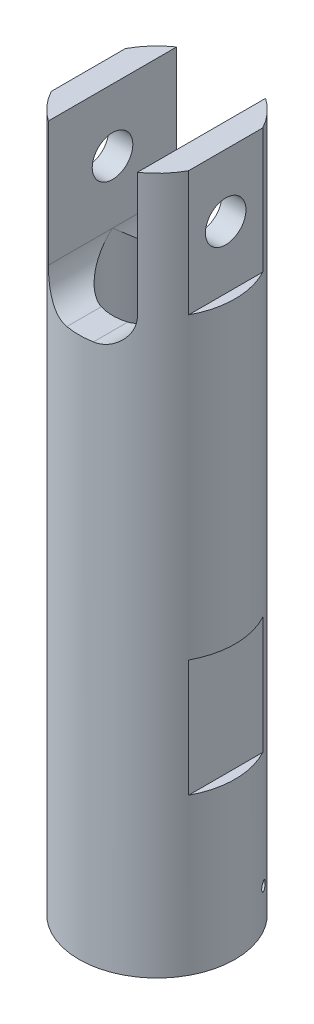
SolidWorks part; units mm, degrees
material "6061-T6 (SS)"
ref_plane "Front Plane" through (0, 0, 0) normal (0, 0, 1) x (1, 0, 0)
ref_plane "Top Plane" through (0, 0, 0) normal (0, 1, 0) x (1, 0, 0)
ref_plane "Right Plane" through (0, 0, 0) normal (1, 0, 0) x (0, 0, -1)
sketch "Sketch1" plane through (0, 0, 0) normal (0, 1, 0) x (1, 0, 0)
  circle A0 centre (0, 0) radius 4.826
  circle A1 centre (0, 0) radius 12.7
  dimension "D1" = 9.652
  dimension "D2" = 25.4
extrude "Socket Head Stop" add sketch "Sketch1" along normal blind 5.08
sketch "Sketch2" plane through (0, 0, 0) normal (0, 1, 0) x (1, 0, 0)
  circle A0 centre (0, 0) radius 12.7 construction
  circle A1 centre (0, 0) radius 12.7
  circle A2 centre (0, 0) radius 7.239
  dimension "D1" = 14.478
extrude "Main Body" add sketch "Sketch2" along normal blind 100.7072
sketch "Sketch6" plane through (0, 0, 0) normal (1, 0, 0) x (0, 0, -1)
  line L0 (-12.7, 0) -> (12.7, 0) construction
  circle A0 centre (0, 90.5472) radius 3.302
  dimension "D2" = 6.604
  dimension "D1" = 90.5472
extrude "Rod End Mounting Holes" cut sketch "Sketch6" against normal through all both and the other way through all
sketch "Sketch3" plane through (0, 0, 0) normal (0, 0, 1) x (1, 0, 0)
  line L0 (-7.239, 100.7072) -> (-7.239, 80.3872)
  line L1 (7.239, 100.7072) -> (-7.239, 100.7072) construction
  line L2 (-2.159, 75.3072) -> (2.159, 75.3072)
  line L3 (7.239, 100.7072) -> (7.239, 80.3872)
  line L4 (12.7, 100.7072) -> (-12.7, 100.7072) construction
  line L5 (12.7, 100.7072) -> (-12.7, 100.7072)
  line L6 (-12.7, 0) -> (12.7, 0) construction
  line L7 (7.239, 100.7072) -> (-7.239, 100.7072)
  line L8 (-12.7, 100.7072) -> (-12.7, 93.8492) construction
  line L9 (-12.7, 100.7072) -> (-11.176, 100.7072)
  line L10 (-12.7, 100.7072) -> (-12.7, 80.3872)
  line L11 (-12.7, 80.3872) -> (-11.176, 80.3872)
  line L12 (-11.176, 100.7072) -> (-11.176, 80.3872)
  line L13 (12.7, 93.8492) -> (12.7, 100.7072) construction
  line L14 (12.7, 100.7072) -> (11.176, 100.7072)
  line L15 (12.7, 100.7072) -> (12.7, 80.3872)
  line L16 (12.7, 80.3872) -> (11.176, 80.3872)
  line L17 (11.176, 100.7072) -> (11.176, 80.3872)
  line L18 (12.7, 0) -> (12.7, 87.2452) construction
  line L19 (12.7, 31.75) -> (11.176, 31.75)
  line L20 (12.7, 31.75) -> (12.7, 12.7)
  line L21 (12.7, 12.7) -> (11.176, 12.7)
  line L22 (11.176, 31.75) -> (11.176, 12.7)
  line L23 (-12.7, 87.2452) -> (-12.7, 0) construction
  line L24 (-12.7, 31.75) -> (-11.176, 31.75)
  line L25 (-12.7, 31.75) -> (-12.7, 12.7)
  line L26 (-12.7, 12.7) -> (-11.176, 12.7)
  line L27 (-11.176, 31.75) -> (-11.176, 12.7)
  arc A0 (-7.239, 80.3872) -> (-2.159, 75.3072) centre (-2.159, 80.3872) ccw
  arc A1 (7.239, 80.3872) -> (2.159, 75.3072) centre (2.159, 80.3872) cw
  point P6 (0, 75.3072)
  point P13 (0, 100.7072)
  point P14 (-7.239, 90.5472)
  point P39 (-11.176, 90.5472)
  point P43 (11.176, 90.5472)
  dimension "D3" = 5.08
  dimension "D1" = 14.478
  dimension "D2" = 90.5472
  dimension "D4" = 1.524
  dimension "D5" = 19.05
  dimension "D6" = 12.7
extrude "Rod End Body Holes And Wrench Cuts" cut sketch "Sketch3" against normal through all both and the other way through all contours A1 L3 L5 L0 A0 L2 | L19 L22 L21 L20 | L10 L11 L12 L5 | L5 L17 L16 L15 | L27 L26 L25 L24 region at (0, 88.3663, 0) region at (11.938, 90.5472, 0) region at (-11.938, 90.5472, 0) region at (11.938, 22.225, 0)
sketch "Sketch4" plane through (0, 0, 0) normal (0, -1, 0) x (1, 0, 0)
  circle A0 centre (0, 0) radius 12.7 construction
  circle A1 centre (0, 0) radius 12.7
  circle A2 centre (0, 0) radius 10.414
  dimension "D1" = 20.828
extrude "Rack Cover" add sketch "Sketch4" along normal blind 12.7
ref_axis "Safety Wire Axis" through (0, -18.5609, 0) along (0, 1, 0)
ref_plane "Safety Wire Plane" through (0, 0, 0) normal (-0.866, 0, 0.5) x (0, 1, 0)
sketch "Sketch7" plane through (0, 0, 0) normal (-0.866, 0, 0.5) x (0, 1, 0)
  line L0 (-18.5609, 0) -> (110.378, 0) construction
  line L2 (0, 10.414) -> (0, -10.414) construction
  circle A0 centre (-6.35, 0) radius 0.762
  dimension "D1" = 1.524
  dimension "D2" = 6.35
extrude "Safety Wire Holes" cut sketch "Sketch7" against normal through all both and the other way through all
sketch3d "Steering Arm Mounting"
  line L0 (11.176, 90.5472, 0) -> (-11.176, 90.5472, 0) construction
  circle A0 centre (11.176, 90.5472, 0) radius 3.302 construction
  point P4 (14.478, 90.5472, 0)
  point P5 (0, 90.5472, 0)
